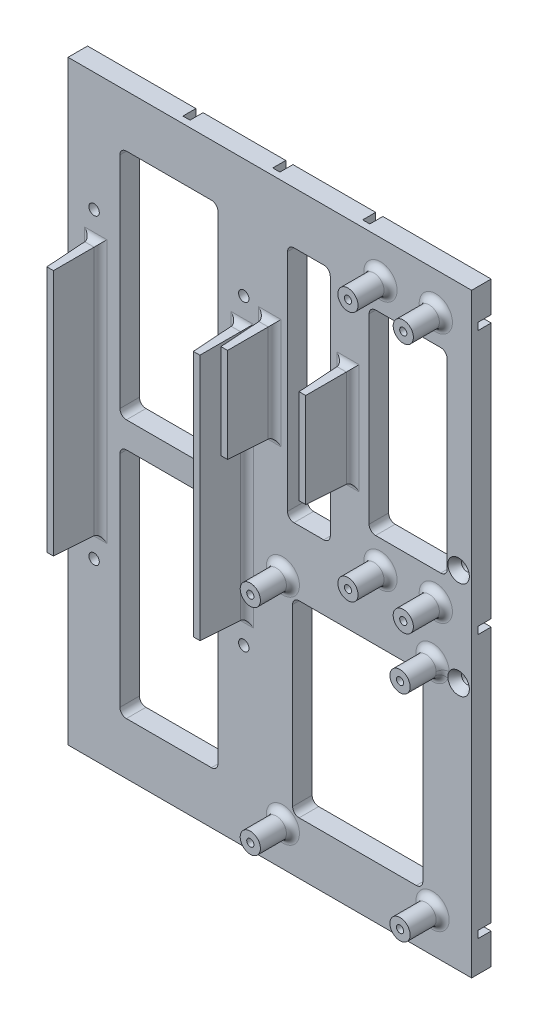
SolidWorks part; units mm, degrees
ref_plane "Front Plane" through (0, 0, 0) normal (1, 0, 0) x (0, 1, 0)
ref_plane "Top Plane" through (0, 0, 0) normal (0, 0, 1) x (0, 1, 0)
ref_plane "Right Plane" through (0, 0, 0) normal (0, 1, 0) x (-1, 0, 0)
sketch "Sketch1" plane through (0, 0, 0) normal (0, 0, 1) x (0, 1, 0)
  line L0 (59.5, 52) -> (59.5, -72)
  line L1 (0, 0) -> (136, 0) construction
  line L2 (0, 0) -> (0, 42) construction
  line L3 (0, 42) -> (136, 42) construction
  line L4 (136, 0) -> (136, 42) construction
  line L5 (-32, 52) -> (151, 52)
  line L6 (-32, 52) -> (-32, -10)
  line L7 (-32, -72) -> (59.5, -72)
  line L8 (151, 52) -> (151, -10)
  line L13 (53, -12) -> (141, -12) construction
  line L14 (53, -12) -> (53, -32) construction
  line L15 (53, -32) -> (141, -32) construction
  line L16 (141, -12) -> (141, -32) construction
  line L17 (97, -32) -> (97, -12) construction
  line L18 (53, -22) -> (141, -22) construction
  line L19 (-22, -12) -> (48, -12) construction
  line L20 (-22, -12) -> (-22, -62) construction
  line L21 (-22, -62) -> (48, -62) construction
  line L22 (48, -12) -> (48, -62) construction
  line L23 (13, -62) -> (13, -12) construction
  line L24 (-22, -37) -> (48, -37) construction
  line L31 (29.5233, 42) -> (106.4767, 42)
  line L37 (68, 0) -> (68, 42) construction
  line L44 (29.5233, 0) -> (106.4767, 0)
  line L45 (82, -32.5) -> (112, -32.5)
  line L46 (82, -11.5) -> (112, -11.5)
  line L47 (0, 21) -> (136, 21) construction
  line L48 (61, -42.5) -> (141, -42.5) construction
  line L49 (61, -42.5) -> (61, -62.5) construction
  line L50 (61, -62.5) -> (141, -62.5) construction
  line L51 (141, -42.5) -> (141, -62.5) construction
  line L52 (101, -62.5) -> (101, -42.5) construction
  line L53 (61, -52.5) -> (141, -52.5) construction
  line L54 (-32, -10) -> (-32, -72)
  line L55 (151, -10) -> (151, -72)
  line L56 (59.5, -72) -> (151, -72)
  line L57 (-32, -10) -> (151, -10)
  line L58 (44.5, 48) -> (59.5, 48) construction
  line L59 (59.5, 48) -> (74.5, 48) construction
  circle A0 centre (44.5, 48) radius 1.6
  circle A1 centre (74.5, 48) radius 1.6
  circle A2 centre (74.5, -68) radius 1.6
  circle A3 centre (44.5, -68) radius 1.6
  circle A4 centre (-20, -14) radius 1.1
  circle A5 centre (46, -14) radius 1.1
  circle A6 centre (-20, -60) radius 1.1
  circle A7 centre (46, -60) radius 1.1
  circle A8 centre (62.5, -44) radius 1.1
  circle A9 centre (139.5, -44) radius 1.1
  circle A10 centre (62.5, -61) radius 1.1
  circle A11 centre (139.5, -61) radius 1.1
  circle A12 centre (114.4767, 44) radius 1.6
  circle A13 centre (114.4767, -2) radius 1.6
  circle A14 centre (21.5233, -2) radius 1.6
  circle A15 centre (21.5233, 44) radius 1.6
  point P18 (81.5244, 47)
  point P19 (27.4376, 46)
  point P27 (26.8592, 47)
  point P141 (101, -52.5)
  point P162 (168.5436, -9.3255)
  point P169 (97, -22)
  point P178 (13, -37)
  point P201 (168.5436, -9.3255)
  dimension "D13" = 3.2
  dimension "D14" = 4
  dimension "D17" = 2.2
  dimension "D20" = 30
  dimension "D25" = 1.5
  dimension "D27" = 2.2
  dimension "D28" = 3.2
  dimension "D29" = 2
  dimension "D32" = 46
  dimension "D1" = 42
  dimension "D2" = 70
  dimension "BatteryLength" = 136
  dimension "D3" = 50
  dimension "D4" = 88
  dimension "D5" = 20
  dimension "D6" = 10
  dimension "D7" = 5
  dimension "D8" = 12
  dimension "D9" = 15
  dimension "D10" = 10
  dimension "D11" = 10
  dimension "D12" = 10
  dimension "D15" = 30
  dimension "D16" = 76.9534
  dimension "D18" = 2
  dimension "D19" = 2
  dimension "D21" = 21
  dimension "D22" = 20
  dimension "D23" = 80
  dimension "D24" = 10
  dimension "D26" = 1.5
  dimension "D30" = 8
  dimension "D31" = 4
  dimension "D33" = 66
extrude "Boss-Extrude1" add sketch "Sketch1" along normal blind 6 contours L7 L8 A11 A10 A9 A8 A2 | A11 | A9 | A8 | A10 | A5 | A4 | A6 | L6 L7 A7 A6 A5 A4 A3 | A7 | L8 L5 A1 | L5 L6 A0 region at (-20.9616, 105.2675, 0) region at (-20.9616, 13.6841, 0) region at (40.9723, 13.7082, 0) region at (40.9306, 105.3052, 0) region at (14, -20, 0) region at (14, 46, 0) region at (60, -20, 0) region at (60, 46, 0) region at (44, 62.5, 0) region at (44, 139.5, 0) region at (61, 62.5, 0) region at (61, 139.5, 0)
extrude "Extrude-Thin1" add sketch "Sketch1<4>" along normal blind 14 draft 2 from surface thin contours L31 | L46 starting at face at (69.6, 74.5, 6) thin type one direction reverse wall 3
sketch "Sketch1<4>" plane through (0, 0, 0) normal (0, 0, 1) x (0, 1, 0) same geometry as "Sketch1"
extrude "Extrude-Thin2" add sketch "Sketch1<5>" along normal blind 14 draft 2 from surface thin contours L45 | L44 starting at face at (69.6, 74.5, 6) thin type one direction wall 3
sketch "Sketch1<5>" plane through (0, 0, 0) normal (0, 0, 1) x (0, 1, 0) same geometry as "Sketch1"
extrude "Extrude-Thin3" add sketch "Sketch1<6>" along normal blind 10 from surface thin contours A5 | A4 | A7 | A6 | A11 | A9 | A8 | A10 starting at face at (69.6, 74.5, 6) thin type one direction wall 2
sketch "Sketch1<6>" plane through (0, 0, 0) normal (0, 0, 1) x (0, 1, 0) same geometry as "Sketch1"
sketch "Sketch2" plane through (0, -32, 0) normal (0, -1, 0) x (1, 0, 0)
  line L1 (11.1, 4) -> (8.9, 4)
  line L2 (11.1, 4) -> (11.1, 0)
  line L3 (11.1, 0) -> (8.9, 0)
  line L4 (8.9, 4) -> (8.9, 0)
  line L5 (10, 0) -> (10, 6) construction
  line L6 (11.1, 2) -> (8.9, 2) construction
  line L7 (-52, 0) -> (72, 0) construction
  line L8 (72, 6) -> (72, 0) construction
  line L9 (-52, 6) -> (-52, 0) construction
  point P76 (10, 2)
  dimension "D1" = 2.2
  dimension "D2" = 4
extrude "Cut-Extrude2" cut sketch "Sketch2" against normal through all
sketch "Sketch3" plane through (72, 0, 0) normal (1, 0, 0) x (0, 1, 0)
  line L0 (-32, 0) -> (151, 0) construction
  line L1 (60.6, 4) -> (58.4, 4)
  line L2 (60.6, 4) -> (60.6, 0)
  line L3 (60.6, 0) -> (58.4, 0)
  line L4 (58.4, 4) -> (58.4, 0)
  line L5 (59.5, 0) -> (59.5, 4) construction
  line L6 (60.6, 2) -> (58.4, 2) construction
  line L7 (151, 6) -> (151, 0) construction
  line L8 (-32, 6) -> (-32, 0) construction
  line L9 (141.5, 2) -> (139.3, 2) construction
  line L10 (-22.5, 4) -> (-20.3, 4)
  line L11 (-22.5, 4) -> (-22.5, 0)
  line L12 (-22.5, 0) -> (-20.3, 0)
  line L13 (-20.3, 4) -> (-20.3, 0)
  line L14 (-21.4, 0) -> (-21.4, 4) construction
  line L15 (-22.5, 2) -> (-20.3, 2) construction
  line L16 (140.4, 0) -> (140.4, 4) construction
  line L17 (139.3, 4) -> (139.3, 0)
  line L18 (141.5, 0) -> (139.3, 0)
  line L19 (141.5, 4) -> (141.5, 0)
  line L20 (141.5, 4) -> (139.3, 4)
  point P26 (140.4, 2)
  point P56 (59.5, 2)
  point P87 (-21.4, 2)
  dimension "D1" = 2.2
  dimension "D2" = 4
  dimension "D3" = 9.5
  dimension "D4" = 2.2
  dimension "D5" = 4
extrude "Cut-Extrude3" cut sketch "Sketch3" against normal through all
sketch "Sketch4" plane through (0, -32, 0) normal (0, -1, 0) x (1, 0, 0)
  line L0 (11.1, 0) -> (72, 0) construction
  line L1 (36.52, 4) -> (38.72, 4)
  line L2 (36.52, 4) -> (36.52, 0)
  line L3 (36.52, 0) -> (38.72, 0)
  line L4 (38.72, 4) -> (38.72, 0)
  line L5 (37.62, 0) -> (37.62, 4) construction
  line L6 (36.52, 2) -> (38.72, 2) construction
  line L7 (72, 6) -> (72, 0) construction
  line L8 (10, 6) -> (10, 0) construction
  line L9 (-52, 6) -> (72, 6) construction
  line L10 (-16.52, 2) -> (-18.72, 2) construction
  line L11 (-17.62, 0) -> (-17.62, 4) construction
  line L12 (-18.72, 4) -> (-18.72, 0)
  line L13 (-16.52, 0) -> (-18.72, 0)
  line L14 (-16.52, 4) -> (-16.52, 0)
  line L15 (-16.52, 4) -> (-18.72, 4)
  point P14 (0, 0)
  point P15 (0, 0)
  point P24 (-17.62, 2)
  point P60 (37.62, 2)
  dimension "D1" = 2.2
  dimension "D2" = 33.28
  dimension "D3" = 4
extrude "Cut-Extrude4" cut sketch "Sketch4" against normal up to next
ref_plane "Plane1" through (0, 59.5, 0) normal (0, -1, 0) x (-1, 0, 0)
mirror "Mirror1" about plane through (0, 59.5, 0) normal (0, -1, 0) of "Cut-Extrude4"
chamfer "Chamfer1" distance 1.7 distance2 2.5 4 edges at (69.6, 44.5, 6) (69.6, 74.5, 6) (-46.4, 44.5, 6) (-46.4, 74.5, 6) first distance on face at (64.1, 139.5, 6)
fillet "Fillet1" radius 2 26 edges at (47.1, 62.5, 6) (64.1, 139.5, 6) (47.1, 139.5, 6) (17.1, 46, 6) (17.1, -20, 6) (63.1, -20, 6) (63.1, 46, 6) (64.1, 62.5, 6) (34, 82, 6) (32.5, 97, 6) (34, 112, 6) (35.5, 97, 6) (10, 112, 6) (8.5, 97, 6) (11.5, 97, 6) (10, 82, 6) (1.5, 29.5233, 6) (0, 68, 6) (3, 68, 6) (1.5, 106.4767, 6) (-43.5, 106.4767, 6) (-43.5, 29.5233, 6) (-45, 91.1757, 6) (-45, 36.3243, 6) (-42, 68, 6) (-45, 59.5, 6)
sketch "Sketch5" plane through (0, 0, 6) normal (0, 0, 1) x (1, 0, 0)
  line L0 (-52, 151) -> (72, 151) construction
  line L1 (-34.0686, 135) -> (-7.9314, 135)
  line L2 (-36.0686, 133) -> (-36.0686, 65.5)
  line L3 (-34.0686, 63.5) -> (-7.9314, 63.5)
  line L4 (-5.9314, 133) -> (-5.9314, 65.5)
  line L5 (-21, 63.5) -> (-21, 135) construction
  line L6 (-36.0686, 99.25) -> (-5.9314, 99.25) construction
  line L7 (19, 41.8757) -> (55, 41.8757)
  line L8 (17, 39.8757) -> (17, -13.8757)
  line L9 (19, -15.8757) -> (55, -15.8757)
  line L10 (57, 39.8757) -> (57, -13.8757)
  line L11 (37, -15.8757) -> (37, 41.8757) construction
  line L12 (17, 13) -> (57, 13) construction
  line L13 (42.5, 131) -> (62.5, 131)
  line L14 (40.5, 129) -> (40.5, 73)
  line L15 (42.5, 71) -> (62.5, 71)
  line L16 (64.5, 129) -> (64.5, 73)
  line L17 (52.5, 71) -> (52.5, 131) construction
  line L18 (40.5, 101) -> (64.5, 101) construction
  line L19 (-34.0686, 55.5) -> (-7.9314, 55.5)
  line L20 (-36.0686, 53.5) -> (-36.0686, -14)
  line L21 (-34.0686, -16) -> (-7.9314, -16)
  line L22 (-5.9314, 53.5) -> (-5.9314, -14)
  line L23 (-21, -16) -> (-21, 55.5) construction
  line L24 (-36.0686, 19.75) -> (-5.9314, 19.75) construction
  line L25 (-1.9314, 27.5919) -> (-1.9314, 108.4081) construction
  line L26 (-40.0686, 108.4081) -> (-40.0686, 27.5919) construction
  line L27 (-40.0686, 108.4081) -> (-40.0686, 27.5919) construction
  line L28 (-52, 59.5) -> (-1.9314, 59.5) construction
  line L29 (-52, -32) -> (72, -32) construction
  line L30 (30.5686, 80.0686) -> (30.5686, 113.9314) construction
  line L31 (14, 46) -> (60, 46) construction
  line L32 (14, 46) -> (14, -20) construction
  line L33 (14, -20) -> (60, -20) construction
  line L34 (60, 46) -> (60, -20) construction
  line L35 (17.4314, 135) -> (26.5686, 135)
  line L36 (15.4314, 133) -> (15.4314, 63.8757)
  line L37 (17.4314, 61.8757) -> (26.5686, 61.8757)
  line L38 (28.5686, 133) -> (28.5686, 63.8757)
  line L39 (-52, -32) -> (-52, 151) construction
  line L40 (13.4314, 113.9314) -> (13.4314, 80.0686) construction
  circle A0 centre (60, -20) radius 1.1 construction
  arc A1 (62.5, 71) -> (64.5, 73) centre (62.5, 73) ccw
  arc A2 (65.0995, 46.0738) -> (64.7263, 44.0838) centre (60, 46) ccw construction
  circle A3 centre (14, 46) radius 5.1 construction
  circle A4 centre (14, -20) radius 5.1 construction
  circle A5 centre (60, -20) radius 5.1 construction
  circle A6 centre (44, 139.5) radius 1.1 construction
  circle A7 centre (44, 62.5) radius 1.1 construction
  arc A8 (62.5, 131) -> (64.5, 129) centre (62.5, 129) cw
  arc A9 (42.5, 131) -> (40.5, 129) centre (42.5, 129) ccw
  arc A10 (40.5, 73) -> (42.5, 71) centre (42.5, 73) ccw
  arc A11 (26.5686, 61.8757) -> (28.5686, 63.8757) centre (26.5686, 63.8757) ccw
  arc A12 (15.4314, 63.8757) -> (17.4314, 61.8757) centre (17.4314, 63.8757) ccw
  arc A13 (26.5686, 135) -> (28.5686, 133) centre (26.5686, 133) cw
  arc A14 (17.4314, 135) -> (15.4314, 133) centre (17.4314, 133) ccw
  arc A15 (19, 41.8757) -> (17, 39.8757) centre (19, 39.8757) ccw
  arc A16 (55, 41.8757) -> (57, 39.8757) centre (55, 39.8757) cw
  arc A17 (55, -15.8757) -> (57, -13.8757) centre (55, -13.8757) ccw
  arc A18 (17, -13.8757) -> (19, -15.8757) centre (19, -13.8757) ccw
  arc A19 (-7.9314, -16) -> (-5.9314, -14) centre (-7.9314, -14) ccw
  arc A20 (-36.0686, -14) -> (-34.0686, -16) centre (-34.0686, -14) ccw
  arc A21 (-34.0686, 55.5) -> (-36.0686, 53.5) centre (-34.0686, 53.5) ccw
  arc A22 (-7.9314, 55.5) -> (-5.9314, 53.5) centre (-7.9314, 53.5) cw
  arc A23 (-7.9314, 63.5) -> (-5.9314, 65.5) centre (-7.9314, 65.5) ccw
  arc A24 (-36.0686, 65.5) -> (-34.0686, 63.5) centre (-34.0686, 65.5) ccw
  arc A25 (-7.9314, 135) -> (-5.9314, 133) centre (-7.9314, 133) cw
  arc A26 (-34.0686, 135) -> (-36.0686, 133) centre (-34.0686, 133) ccw
  point P51 (64.5, 71)
  point P58 (64.5, 131)
  point P61 (40.5, 131)
  point P82 (-21, 19.75)
  point P85 (17, 41.8757)
  point P88 (57, 41.8757)
  point P91 (57, -15.8757)
  point P94 (17, -15.8757)
  point P111 (0, 0)
  point P182 (37, 13)
  point P227 (52.5, 101)
  point P264 (-21, 99.25)
  dimension "D13" = 2
  dimension "D1" = 16
  dimension "D2" = 4
  dimension "D3" = 4
  dimension "D4" = 4
  dimension "D5" = 16
  dimension "D6" = 40
  dimension "D7" = 24
  dimension "D8" = 60
  dimension "D9" = 2
  dimension "D10" = 2
  dimension "D11" = 20
  dimension "D12" = 16
extrude "Cut-Extrude5" cut sketch "Sketch5" against normal through all
